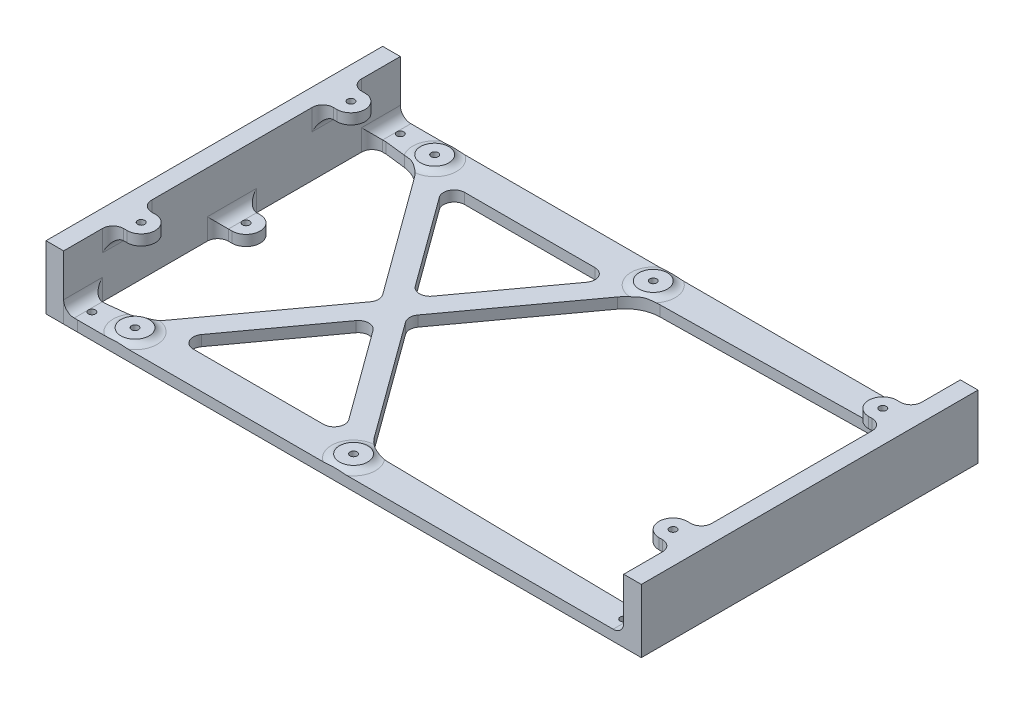
SolidWorks part; units mm, degrees
ref_plane "Front Plane" through (0, 0, 0) normal (0, 0, 1) x (1, 0, 0)
ref_plane "Top Plane" through (0, 0, 0) normal (0, 1, 0) x (1, 0, 0)
ref_plane "Right Plane" through (0, 0, 0) normal (1, 0, 0) x (0, 0, -1)
sketch "Sketch1" plane through (0, 20, 0) normal (0, 1, 0) x (1, 0, 0)
  line L11 (-48.875, 4.25) -> (-53.875, 4.25)
  line L12 (-53.875, 4.25) -> (-53.875, -91.25)
  line L13 (-53.875, -91.25) -> (-48.875, -91.25)
  line L14 (-48.875, -91.25) -> (-44.875, -91.25)
  line L15 (-44.875, -83.25) -> (-45.875, -83.25)
  line L16 (-48.875, -80.25) -> (-48.875, -50.5)
  line L17 (-45.875, -47.5) -> (-44.875, -47.5)
  line L18 (-44.875, -39.5) -> (-45.875, -39.5)
  line L19 (-48.875, -36.5) -> (-48.875, -6.75)
  line L20 (-45.875, -3.75) -> (-44.875, -3.75)
  line L21 (-44.875, 4.25) -> (-48.875, 4.25)
  line L22 (-48.875, 4.25) -> (-53.875, 4.25)
  line L23 (-53.875, 4.25) -> (-53.875, -91.25)
  line L24 (-53.875, -91.25) -> (-48.875, -91.25)
  line L25 (-48.875, -91.25) -> (-44.875, -91.25)
  line L26 (-44.875, -83.25) -> (-45.875, -83.25)
  line L27 (-48.875, -80.25) -> (-48.875, -50.5)
  line L28 (-45.875, -47.5) -> (-44.875, -47.5)
  line L29 (-44.875, -39.5) -> (-45.875, -39.5)
  line L30 (-48.875, -36.5) -> (-48.875, -6.75)
  line L31 (-45.875, -3.75) -> (-44.875, -3.75)
  line L32 (-44.875, 4.25) -> (-48.875, 4.25)
  line L33 (115, 4.25) -> (110, 4.25)
  line L34 (110, 4.25) -> (106, 4.25)
  line L35 (106, -3.75) -> (107, -3.75)
  line L36 (110, -6.75) -> (110, -36.5)
  line L37 (107, -39.5) -> (106, -39.5)
  line L38 (106, -47.5) -> (107, -47.5)
  line L39 (110, -50.5) -> (110, -80.25)
  line L40 (107, -83.25) -> (106, -83.25)
  line L41 (106, -91.25) -> (110, -91.25)
  line L42 (110, -91.25) -> (115, -91.25)
  line L43 (115, -91.25) -> (115, 4.25)
  line L44 (115, 4.25) -> (110, 4.25)
  line L45 (110, 4.25) -> (106, 4.25)
  line L46 (106, -3.75) -> (107, -3.75)
  line L47 (110, -6.75) -> (110, -36.5)
  line L48 (107, -39.5) -> (106, -39.5)
  line L49 (106, -47.5) -> (107, -47.5)
  line L50 (110, -50.5) -> (110, -80.25)
  line L51 (107, -83.25) -> (106, -83.25)
  line L52 (106, -91.25) -> (110, -91.25)
  line L53 (110, -91.25) -> (115, -91.25)
  line L54 (115, -91.25) -> (115, 4.25)
  circle A0 centre (106, -87.25) radius 1 construction
  circle A1 centre (106, -43.5) radius 1 construction
  circle A2 centre (106, -87.25) radius 1
  circle A3 centre (106, -43.5) radius 1
  circle A4 centre (-44.875, -87.25) radius 1 construction
  circle A5 centre (-44.875, -43.5) radius 1 construction
  circle A6 centre (-44.875, 0.25) radius 1 construction
  arc A7 (-44.875, -91.25) -> (-44.875, -83.25) centre (-44.875, -87.25) ccw
  arc A8 (-48.875, -80.25) -> (-45.875, -83.25) centre (-45.875, -80.25) ccw
  arc A9 (-45.875, -47.5) -> (-48.875, -50.5) centre (-45.875, -50.5) ccw
  arc A10 (-44.875, -47.5) -> (-44.875, -39.5) centre (-44.875, -43.5) ccw
  arc A11 (-48.875, -36.5) -> (-45.875, -39.5) centre (-45.875, -36.5) ccw
  arc A12 (-45.875, -3.75) -> (-48.875, -6.75) centre (-45.875, -6.75) ccw
  arc A13 (-44.875, -3.75) -> (-44.875, 4.25) centre (-44.875, 0.25) ccw
  arc A14 (-44.875, -91.25) -> (-44.875, -83.25) centre (-44.875, -87.25) ccw
  arc A15 (-48.875, -80.25) -> (-45.875, -83.25) centre (-45.875, -80.25) ccw
  arc A16 (-45.875, -47.5) -> (-48.875, -50.5) centre (-45.875, -50.5) ccw
  arc A17 (-44.875, -47.5) -> (-44.875, -39.5) centre (-44.875, -43.5) ccw
  arc A18 (-48.875, -36.5) -> (-45.875, -39.5) centre (-45.875, -36.5) ccw
  arc A19 (-45.875, -3.75) -> (-48.875, -6.75) centre (-45.875, -6.75) ccw
  arc A20 (-44.875, -3.75) -> (-44.875, 4.25) centre (-44.875, 0.25) ccw
  arc A21 (106, 4.25) -> (106, -3.75) centre (106, 0.25) ccw
  arc A22 (110, -6.75) -> (107, -3.75) centre (107, -6.75) ccw
  arc A23 (107, -39.5) -> (110, -36.5) centre (107, -36.5) ccw
  arc A24 (106, -39.5) -> (106, -47.5) centre (106, -43.5) ccw
  arc A25 (110, -50.5) -> (107, -47.5) centre (107, -50.5) ccw
  arc A26 (107, -83.25) -> (110, -80.25) centre (107, -80.25) ccw
  arc A27 (106, -83.25) -> (106, -91.25) centre (106, -87.25) ccw
  arc A28 (106, 4.25) -> (106, -3.75) centre (106, 0.25) ccw
  arc A29 (110, -6.75) -> (107, -3.75) centre (107, -6.75) ccw
  arc A30 (107, -39.5) -> (110, -36.5) centre (107, -36.5) ccw
  arc A31 (106, -39.5) -> (106, -47.5) centre (106, -43.5) ccw
  arc A32 (110, -50.5) -> (107, -47.5) centre (107, -50.5) ccw
  arc A33 (107, -83.25) -> (110, -80.25) centre (107, -80.25) ccw
  arc A34 (106, -83.25) -> (106, -91.25) centre (106, -87.25) ccw
  circle A35 centre (106, 0.25) radius 1 construction
  circle A36 centre (-44.875, -87.25) radius 1
  circle A37 centre (-44.875, -43.5) radius 1
  circle A38 centre (-44.875, 0.25) radius 1
  circle A39 centre (106, 0.25) radius 1
  dimension "D1" = 0
  dimension "D2" = 0
extrude "LEVEL 1 mating surface" add sketch "Sketch1" along normal blind 3
sketch "Sketch2" plane through (0, 23, 0) normal (0, 1, 0) x (1, 0, 0)
  line L1 (-53.875, 4.25) -> (-48.875, 4.25)
  line L2 (-53.875, 4.25) -> (-53.875, -91.25)
  line L3 (-53.875, -91.25) -> (-48.875, -91.25)
  line L4 (-48.875, 4.25) -> (-48.875, -91.25)
  line L5 (110, 4.25) -> (115, 4.25)
  line L6 (110, 4.25) -> (110, -91.25)
  line L7 (110, -91.25) -> (115, -91.25)
  line L8 (115, 4.25) -> (115, -91.25)
extrude "LEVEL 3 riser" add sketch "Sketch2" along normal blind 15
sketch "Sketch3" plane through (0, 38, 0) normal (0, 1, 0) x (1, 0, 0)
  line L2 (-48.875, -91.25) -> (-48.875, 4.25) construction
  line L4 (-48.875, -6.75) -> (-48.875, -20.75)
  line L10 (-44.875, -43.5) -> (106, -43.5) construction
  line L11 (-44.875, -77.25) -> (-45.875, -77.25)
  line L19 (-45.875, -69.25) -> (-44.875, -69.25)
  line L23 (-45.875, -17.75) -> (-44.875, -17.75)
  line L28 (-48.875, -80.25) -> (-48.875, -66.25)
  line L29 (30.5625, -3.5) -> (30.5625, -83.5) construction
  line L36 (-44.875, -9.75) -> (-45.875, -9.75)
  line L38 (106, -9.75) -> (107, -9.75)
  line L39 (110, -80.25) -> (110, -66.25)
  line L40 (107, -17.75) -> (106, -17.75)
  line L41 (107, -69.25) -> (106, -69.25)
  line L42 (106, -77.25) -> (107, -77.25)
  line L43 (110, -6.75) -> (110, -20.75)
  circle A9 centre (-44.875, -73.25) radius 1
  arc A10 (-48.875, -80.25) -> (-45.875, -77.25) centre (-45.875, -80.25) cw
  arc A11 (-44.875, -69.25) -> (-44.875, -77.25) centre (-44.875, -73.25) cw
  arc A21 (-45.875, -17.75) -> (-48.875, -20.75) centre (-45.875, -20.75) ccw
  arc A31 (-45.875, -69.25) -> (-48.875, -66.25) centre (-45.875, -66.25) cw
  circle A32 centre (106, -13.75) radius 1
  arc A40 (-44.875, -17.75) -> (-44.875, -9.75) centre (-44.875, -13.75) ccw
  arc A41 (-48.875, -6.75) -> (-45.875, -9.75) centre (-45.875, -6.75) ccw
  circle A42 centre (-44.875, -13.75) radius 1
  arc A43 (110, -6.75) -> (107, -9.75) centre (107, -6.75) cw
  arc A44 (106, -17.75) -> (106, -9.75) centre (106, -13.75) cw
  arc A45 (107, -69.25) -> (110, -66.25) centre (107, -66.25) ccw
  arc A46 (107, -17.75) -> (110, -20.75) centre (107, -20.75) cw
  arc A47 (106, -69.25) -> (106, -77.25) centre (106, -73.25) ccw
  arc A48 (110, -80.25) -> (107, -77.25) centre (107, -80.25) ccw
  circle A49 centre (106, -73.25) radius 1
  point P25 (30.5625, -43.5)
  point P26 (30.5625, -43.5)
  dimension "D1" = 2
  dimension "D2" = 4
  dimension "D3" = 3
  dimension "D4" = 80
extrude "LEVEL 3 screwholes" add sketch "Sketch3" against normal blind 3
fillet "Fillet1" radius 3 5 edges at (-48.875, 23, 1.25) (-48.875, 35, 13.75) (-48.875, 23, 43.5) (-48.875, 23, 85.75) (-48.875, 35, 73.25)
fillet "Fillet2" radius 3 5 edges at (110, 23, 85.75) (110, 23, 43.5) (110, 23, 1.25) (110, 35, 13.75) (110, 35, 73.25)
sketch "Sketch4" plane through (0, 20, 0) normal (0, -1, 0) x (1, 0, 0)
  line L0 (-53.875, -4.25) -> (-53.875, 91.25) construction
  line L1 (-33.875, 1) -> (28.125, 1) construction
  line L2 (-33.875, 1) -> (-33.875, 86) construction
  line L3 (-33.875, 86) -> (28.125, 86) construction
  line L4 (28.125, 1) -> (28.125, 86) construction
  line L5 (-53.875, -4.25) -> (-53.875, 91.25) construction
  circle A0 centre (-33.875, 1) radius 1
  circle A1 centre (28.125, 1) radius 1
  circle A2 centre (28.125, 86) radius 1
  circle A3 centre (-33.875, 86) radius 1
  circle A4 centre (-33.875, 1) radius 4
  circle A5 centre (28.125, 1) radius 4
  circle A6 centre (28.125, 86) radius 4
  circle A7 centre (-33.875, 86) radius 4
  point P8 (-26.1744, -5.6141)
  point P11 (-53.875, 43.5)
  point P12 (-33.875, 43.5)
  dimension "D3" = 2
  dimension "D1" = 62
  dimension "D2" = 85
  dimension "D5" = 20
  dimension "D4" = 3
extrude "Amp screwholes" add sketch "Sketch4" against normal up to surface (3 mm away) separate body up to face at (-44.7083, 23, -0.0833)
sketch "Sketch5" plane through (0, 20, 0) normal (0, -1, 0) x (1, 0, 0)
  line L0 (-44.875, 91.25) -> (106, 91.25)
  line L1 (106, -4.25) -> (-44.875, -4.25)
  line L2 (-44.875, 3.75) -> (-34.3362, 4.9733)
  line L3 (-33.875, 5) -> (28.125, 5)
  line L4 (106, 3.75) -> (28.1892, 4.9995)
  line L5 (-44.875, 91.25) -> (106, 91.25)
  line L6 (28.125, 82) -> (-33.875, 82)
  line L7 (106, 83.25) -> (28.1892, 82.0005)
  line L8 (-44.875, 83.25) -> (-34.3362, 82.0267)
  line L11 (-48.875, -4.25) -> (-44.875, -4.25)
  line L12 (-44.875, 3.75) -> (-45.875, 3.75)
  line L13 (-48.875, 6.75) -> (-48.875, 36.5)
  line L14 (-45.875, 39.5) -> (-44.875, 39.5)
  line L15 (-44.875, 47.5) -> (-45.875, 47.5)
  line L16 (-48.875, 50.5) -> (-48.875, 80.25)
  line L17 (-45.875, 83.25) -> (-44.875, 83.25)
  line L18 (-44.875, 91.25) -> (-48.875, 91.25)
  line L19 (-48.875, 91.25) -> (-53.875, 91.25)
  line L20 (-53.875, 91.25) -> (-53.875, -4.25)
  line L21 (-53.875, -4.25) -> (-48.875, -4.25)
  line L22 (-48.875, -4.25) -> (-44.875, -4.25)
  line L23 (-44.875, 3.75) -> (-45.875, 3.75)
  line L24 (-48.875, 6.75) -> (-48.875, 36.5)
  line L25 (-45.875, 39.5) -> (-44.875, 39.5)
  line L26 (-44.875, 47.5) -> (-45.875, 47.5)
  line L27 (-48.875, 50.5) -> (-48.875, 80.25)
  line L28 (-45.875, 83.25) -> (-44.875, 83.25)
  line L29 (-44.875, 91.25) -> (-48.875, 91.25)
  line L30 (-48.875, 91.25) -> (-53.875, 91.25)
  line L31 (-53.875, 91.25) -> (-53.875, -4.25)
  line L32 (-53.875, -4.25) -> (-48.875, -4.25)
  line L33 (115, -4.25) -> (115, 91.25)
  line L34 (115, 91.25) -> (110, 91.25)
  line L35 (110, 91.25) -> (106, 91.25)
  line L36 (106, 83.25) -> (107, 83.25)
  line L37 (110, 80.25) -> (110, 50.5)
  line L38 (107, 47.5) -> (106, 47.5)
  line L39 (106, 39.5) -> (107, 39.5)
  line L40 (110, 36.5) -> (110, 6.75)
  line L41 (107, 3.75) -> (106, 3.75)
  line L42 (106, -4.25) -> (110, -4.25)
  line L43 (110, -4.25) -> (115, -4.25)
  line L44 (115, -4.25) -> (115, 91.25)
  line L45 (115, 91.25) -> (110, 91.25)
  line L46 (110, 91.25) -> (106, 91.25)
  line L47 (106, 83.25) -> (107, 83.25)
  line L48 (110, 80.25) -> (110, 50.5)
  line L49 (107, 47.5) -> (106, 47.5)
  line L50 (106, 39.5) -> (107, 39.5)
  line L51 (110, 36.5) -> (110, 6.75)
  line L52 (107, 3.75) -> (106, 3.75)
  line L53 (106, -4.25) -> (110, -4.25)
  line L54 (110, -4.25) -> (115, -4.25)
  circle A0 centre (-44.875, -0.25) radius 1 construction
  circle A1 centre (-44.875, 43.5) radius 1 construction
  circle A2 centre (-44.875, 87.25) radius 1 construction
  circle A3 centre (-44.875, -0.25) radius 1
  circle A4 centre (-44.875, 43.5) radius 1
  circle A5 centre (-44.875, 87.25) radius 1
  circle A6 centre (106, -0.25) radius 1 construction
  arc A7 (-44.875, -4.25) -> (-44.875, 3.75) centre (-44.875, -0.25) ccw
  arc A8 (-48.875, 6.75) -> (-45.875, 3.75) centre (-45.875, 6.75) ccw
  arc A9 (-45.875, 39.5) -> (-48.875, 36.5) centre (-45.875, 36.5) ccw
  arc A10 (-44.875, 39.5) -> (-44.875, 47.5) centre (-44.875, 43.5) ccw
  arc A11 (-48.875, 50.5) -> (-45.875, 47.5) centre (-45.875, 50.5) ccw
  arc A12 (-45.875, 83.25) -> (-48.875, 80.25) centre (-45.875, 80.25) ccw
  arc A13 (-44.875, 83.25) -> (-44.875, 91.25) centre (-44.875, 87.25) ccw
  arc A15 (-48.875, 6.75) -> (-45.875, 3.75) centre (-45.875, 6.75) ccw
  arc A16 (-45.875, 39.5) -> (-48.875, 36.5) centre (-45.875, 36.5) ccw
  arc A17 (-44.875, 39.5) -> (-44.875, 47.5) centre (-44.875, 43.5) ccw
  arc A18 (-48.875, 50.5) -> (-45.875, 47.5) centre (-45.875, 50.5) ccw
  arc A19 (-45.875, 83.25) -> (-48.875, 80.25) centre (-45.875, 80.25) ccw
  circle A21 centre (106, 43.5) radius 1 construction
  circle A22 centre (106, 87.25) radius 1 construction
  circle A23 centre (106, -0.25) radius 1
  circle A24 centre (106, 43.5) radius 1
  circle A25 centre (106, 87.25) radius 1
  circle A26 centre (-33.875, 1) radius 4 construction
  arc A27 (106, 91.25) -> (106, 83.25) centre (106, 87.25) ccw
  arc A28 (110, 80.25) -> (107, 83.25) centre (107, 80.25) ccw
  arc A29 (107, 47.5) -> (110, 50.5) centre (107, 50.5) ccw
  arc A30 (106, 47.5) -> (106, 39.5) centre (106, 43.5) ccw
  arc A31 (110, 36.5) -> (107, 39.5) centre (107, 36.5) ccw
  arc A32 (107, 3.75) -> (110, 6.75) centre (107, 6.75) ccw
  arc A33 (106, 3.75) -> (106, -4.25) centre (106, -0.25) ccw
  arc A35 (110, 80.25) -> (107, 83.25) centre (107, 80.25) ccw
  arc A36 (107, 47.5) -> (110, 50.5) centre (107, 50.5) ccw
  arc A37 (106, 47.5) -> (106, 39.5) centre (106, 43.5) ccw
  arc A38 (110, 36.5) -> (107, 39.5) centre (107, 36.5) ccw
  arc A39 (107, 3.75) -> (110, 6.75) centre (107, 6.75) ccw
  circle A41 centre (28.125, 1) radius 4 construction
  circle A42 centre (28.125, 86) radius 4 construction
  circle A43 centre (-33.875, 86) radius 4 construction
  arc A44 (-33.875, 5) -> (-34.3362, 4.9733) centre (-33.875, 1) ccw
  arc A45 (28.1892, 4.9995) -> (28.125, 5) centre (28.125, 1) ccw
  arc A46 (28.125, 82) -> (28.1892, 82.0005) centre (28.125, 86) ccw
  arc A47 (-34.3362, 82.0267) -> (-33.875, 82) centre (-33.875, 86) ccw
  circle A48 centre (-33.875, 1) radius 1 construction
  circle A49 centre (28.125, 1) radius 1 construction
  circle A50 centre (28.125, 86) radius 1 construction
  circle A51 centre (-33.875, 86) radius 1 construction
  circle A52 centre (-33.875, 1) radius 1
  circle A53 centre (28.125, 1) radius 1
  circle A54 centre (28.125, 86) radius 1
  circle A55 centre (-33.875, 86) radius 1
  line M48 (-48.875, -4.25) -> (-44.875, -4.25)
  arc M49 (-44.875, -4.25) -> (-44.875, 3.75) centre (-44.875, -0.25) ccw
  line M50 (-44.875, 3.75) -> (-45.875, 3.75)
  arc M51 (-45.875, 3.75) -> (-48.875, 6.75) centre (-45.875, 6.75) cw
  line M52 (-48.875, 6.75) -> (-48.875, 36.5)
  arc M53 (-48.875, 36.5) -> (-45.875, 39.5) centre (-45.875, 36.5) cw
  line M54 (-45.875, 39.5) -> (-44.875, 39.5)
  arc M55 (-44.875, 39.5) -> (-44.875, 47.5) centre (-44.875, 43.5) ccw
  line M56 (-44.875, 47.5) -> (-45.875, 47.5)
  arc M57 (-45.875, 47.5) -> (-48.875, 50.5) centre (-45.875, 50.5) cw
  line M58 (-48.875, 50.5) -> (-48.875, 80.25)
  arc M59 (-48.875, 80.25) -> (-45.875, 83.25) centre (-45.875, 80.25) cw
  line M60 (-45.875, 83.25) -> (-44.875, 83.25)
  arc M61 (-44.875, 83.25) -> (-44.875, 91.25) centre (-44.875, 87.25) ccw
  line M62 (-44.875, 91.25) -> (-48.875, 91.25)
  line M63 (-48.875, 91.25) -> (-53.875, 91.25)
  line M64 (-53.875, 91.25) -> (-53.875, -4.25)
  line M65 (-53.875, -4.25) -> (-48.875, -4.25)
  circle M66 centre (-44.875, 87.25) radius 1
  circle M67 centre (-44.875, 43.5) radius 1
  circle M68 centre (-44.875, -0.25) radius 1
  dimension "D1" = 0
  dimension "D2" = 0
extrude "Screwhole links" add sketch "Sketch5" against normal blind 3 contours M65 M48 M49 M50 M51 M52 M53 M54 M55 M56 M57 M58 M59 M60 M61 M62 M63 M64 M66 M68 M67 | L8 A47 L6 A46 L7 L47 A35 L48 A36 L49 A37 L50 A38 L51 A39 L52 L4 A45 L3 A44 L2 L1 L53 L54 L44 L45 L46 L0 A55 A54 A53 A52 A25 A24 A23 M49 M61 region at (-49.8093, 20, 43.5) region at (29.2272, 20, 86.7851) region at (110.9343, 20, 43.5) region at (29.2273, 20, 0.2148)
sketch "Sketch6" plane through (0, 23, 0) normal (0, 1, 0) x (1, 0, 0)
  line L0 (-33.875, -1) -> (28.125, -86) construction
  line L1 (28.125, -1) -> (-33.875, -86) construction
  line L2 (-34.7228, -4.9284) -> (-6.5883, -43.5)
  line L3 (21.4941, -5) -> (-2.875, -38.4092)
  line L4 (-27.2441, -5) -> (-2.875, -38.4092)
  line L5 (28.9297, -4.9876) -> (0.8383, -43.5)
  line L6 (106, -3.75) -> (28.1892, -4.9995) construction
  line L7 (-33.875, -5) -> (28.125, -5) construction
  line L8 (28.9297, -4.9876) -> (28.1892, -4.9995)
  line L9 (-33.875, -5) -> (-27.2441, -5)
  line L10 (-44.875, -3.75) -> (-34.3362, -4.9733) construction
  line L11 (-34.7228, -4.9284) -> (-34.3362, -4.9733)
  line L12 (28.125, -82) -> (-33.875, -82) construction
  line L13 (-44.875, -83.25) -> (-34.3362, -82.0267) construction
  line L14 (28.125, -82) -> (21.4941, -82)
  line L15 (-34.7228, -82.0715) -> (-34.3362, -82.0267)
  line L16 (106, -83.25) -> (28.1892, -82.0005) construction
  line L17 (28.9297, -82.0124) -> (28.1892, -82.0005)
  line L18 (-31.4512, 0.7679) -> (30.5488, -84.2321) construction
  line L19 (-36.2987, -2.7679) -> (25.7013, -87.7679) construction
  line L20 (-27.2441, -82) -> (-33.875, -82)
  line L21 (25.7013, 0.7679) -> (-36.2987, -84.2321) construction
  line L22 (30.5488, -2.7679) -> (-31.4512, -87.7679) construction
  line L23 (21.4941, -5) -> (28.125, -5)
  line L24 (-2.875, -48.5908) -> (21.4941, -82)
  line L25 (-6.5883, -43.5) -> (-34.7228, -82.0715)
  line L26 (0.8383, -43.5) -> (28.9297, -82.0124)
  line L27 (-2.875, -48.5908) -> (-27.2441, -82)
  circle A1 centre (-33.875, -86) radius 1 construction
  arc A2 (-34.3362, -4.9733) -> (-33.875, -5) centre (-33.875, -1) ccw construction
  arc A3 (-34.3362, -4.9733) -> (-33.875, -5) centre (-33.875, -1) ccw
  arc A4 (-33.875, -82) -> (-34.3362, -82.0267) centre (-33.875, -86) ccw construction
  arc A5 (-33.875, -82) -> (-34.3362, -82.0267) centre (-33.875, -86) ccw
  arc A6 (28.1892, -82.0005) -> (28.125, -82) centre (28.125, -86) ccw construction
  arc A7 (28.1892, -82.0005) -> (28.125, -82) centre (28.125, -86) ccw
  arc A8 (28.125, -5) -> (28.1892, -4.9995) centre (28.125, -1) ccw construction
  arc A9 (28.125, -5) -> (28.1892, -4.9995) centre (28.125, -1) ccw
  point P2 (-33.875, -86)
  dimension "D1" = 3
  dimension "D2" = 3
extrude "Amp screwhole reinforcements" add sketch "Sketch6" against normal up to surface (3 mm away) up to face at (30.5625, 20, 43.5)
fillet "Fillet3" radius 3 8 edges at (-27.2441, 21.5, 82) (21.4941, 21.5, 82) (-2.875, 21.5, 48.5908) (0.8383, 21.5, 43.5) (-6.5883, 21.5, 43.5) (-2.875, 21.5, 38.4092) (21.4941, 21.5, 5) (-27.2441, 21.5, 5)
fillet "Fillet5" radius 10 4 edges at (-34.7228, 21.5, 82.0715) (-34.7228, 21.5, 4.9284) (28.9297, 21.5, 82.0124) (28.9297, 21.5, 4.9876)
sketch "Sketch7" plane through (0, 23, 0) normal (0, 1, 0) x (1, 0, 0)
  circle A0 centre (28.125, -86) radius 1 construction
  circle A1 centre (28.125, -1) radius 1 construction
  circle A2 centre (-33.875, -1) radius 1 construction
  circle A3 centre (-33.875, -86) radius 1 construction
  circle A4 centre (28.125, -86) radius 1
  circle A5 centre (28.125, -1) radius 1
  circle A6 centre (-33.875, -1) radius 1
  circle A7 centre (-33.875, -86) radius 1
  circle A8 centre (28.125, -86) radius 4
  circle A9 centre (28.125, -1) radius 4
  circle A10 centre (-33.875, -1) radius 4
  circle A11 centre (-33.875, -86) radius 4
  dimension "D1" = 3
extrude "Amp standoffs" add sketch "Sketch7" along normal blind 1
fillet "Fillet4" radius 3 4 edges at (28.125, 23, 5) (28.125, 23, 90) (-33.875, 23, 5) (-33.875, 23, 90)
